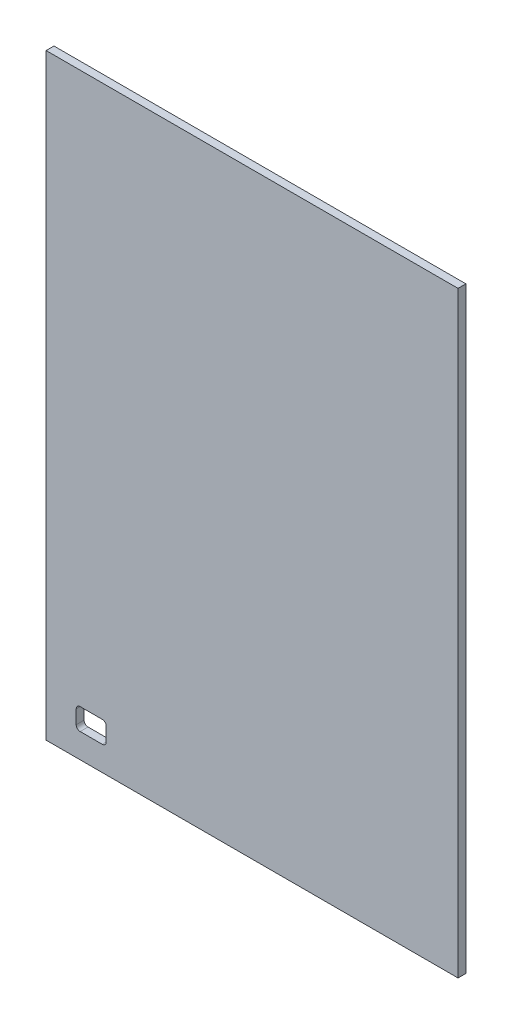
SolidWorks part; units mm, degrees
ref_plane "Front Plane" through (0, 0, 0) normal (0, 0, 1) x (1, 0, 0)
ref_plane "Top Plane" through (0, 0, 0) normal (0, 1, 0) x (1, 0, 0)
ref_plane "Right Plane" through (0, 0, 0) normal (1, 0, 0) x (0, 0, -1)
sketch "Sketch1" plane through (0, 0, 0) normal (0, 0, 1) x (1, 0, 0)
  line L1 (0, 0) -> (420, 0)
  line L2 (0, 0) -> (0, 608.95)
  line L3 (0, 608.95) -> (420, 608.95)
  line L4 (420, 0) -> (420, 608.95)
  line L12 (61.3, 43) -> (61.3, 29) construction
  line L13 (57.3, 25) -> (34.7, 25) construction
  line L14 (30.7, 29) -> (30.7, 43) construction
  line L15 (34.7, 47) -> (57.3, 47) construction
  line L16 (61.3, 43) -> (61.3, 29)
  line L17 (57.3, 25) -> (34.7, 25)
  line L18 (30.7, 29) -> (30.7, 43)
  line L19 (34.7, 47) -> (57.3, 47)
  arc A8 (59.6218, 46.2572) -> (57.3, 47) centre (57.3, 43) ccw construction
  arc A9 (60.6102, 45.2456) -> (59.6218, 46.2572) centre (57.3, 43) ccw construction
  arc A10 (61.3, 43) -> (60.6102, 45.2456) centre (57.3, 43) ccw construction
  arc A11 (60.6102, 26.7544) -> (61.3, 29) centre (57.3, 29) ccw construction
  arc A12 (59.6218, 25.7428) -> (60.6102, 26.7544) centre (57.3, 29) ccw construction
  arc A13 (57.3, 25) -> (59.6218, 25.7428) centre (57.3, 29) ccw construction
  arc A14 (32.3782, 25.7428) -> (34.7, 25) centre (34.7, 29) ccw construction
  arc A15 (31.3898, 26.7544) -> (32.3782, 25.7428) centre (34.7, 29) ccw construction
  arc A16 (30.7, 29) -> (31.3898, 26.7544) centre (34.7, 29) ccw construction
  arc A17 (31.3898, 45.2456) -> (30.7, 43) centre (34.7, 43) ccw construction
  arc A18 (32.3782, 46.2572) -> (31.3898, 45.2456) centre (34.7, 43) ccw construction
  arc A19 (34.7, 47) -> (32.3782, 46.2572) centre (34.7, 43) ccw construction
  arc A20 (59.6218, 46.2572) -> (57.3, 47) centre (57.3, 43) ccw
  arc A21 (60.6102, 45.2456) -> (59.6218, 46.2572) centre (57.3, 43) ccw
  arc A22 (61.3, 43) -> (60.6102, 45.2456) centre (57.3, 43) ccw
  arc A23 (60.6102, 26.7544) -> (61.3, 29) centre (57.3, 29) ccw
  arc A24 (59.6218, 25.7428) -> (60.6102, 26.7544) centre (57.3, 29) ccw
  arc A25 (57.3, 25) -> (59.6218, 25.7428) centre (57.3, 29) ccw
  arc A26 (32.3782, 25.7428) -> (34.7, 25) centre (34.7, 29) ccw
  arc A27 (31.3898, 26.7544) -> (32.3782, 25.7428) centre (34.7, 29) ccw
  arc A28 (30.7, 29) -> (31.3898, 26.7544) centre (34.7, 29) ccw
  arc A29 (31.3898, 45.2456) -> (30.7, 43) centre (34.7, 43) ccw
  arc A30 (32.3782, 46.2572) -> (31.3898, 45.2456) centre (34.7, 43) ccw
  arc A31 (34.7, 47) -> (32.3782, 46.2572) centre (34.7, 43) ccw
  dimension "D1" = 608.95
  dimension "D2" = 420
extrude "Boss-Extrude1" add sketch "Sketch1" along normal blind 8
